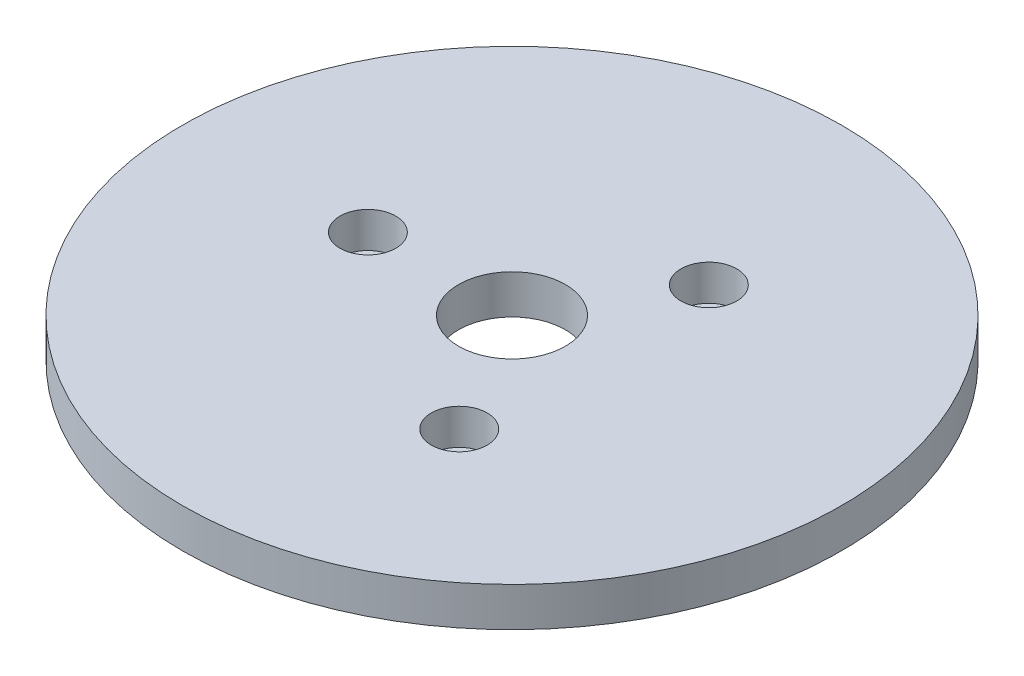
SolidWorks part; units mm, degrees
ref_plane "Front Plane" through (0, 0, 0) normal (0, 0, 1) x (1, 0, 0)
ref_plane "Top Plane" through (0, 0, 0) normal (0, 1, 0) x (1, 0, 0)
ref_plane "Right Plane" through (0, 0, 0) normal (1, 0, 0) x (0, 0, -1)
sketch "Sketch1" plane through (0, 0, 0) normal (0, 1, 0) x (1, 0, 0)
  circle A0 centre (0, 0) radius 92.5
  dimension "FLANGE_OD" = 185
extrude "Boss-Extrude1" add sketch "Sketch1" along normal blind 11
sketch "Sketch2" plane through (0, 0, 0) normal (0, 1, 0) x (1, 0, 0)
  circle A0 centre (0, 0) radius 15
  dimension "BORE_D" = 30
extrude "Cut-Extrude1" cut sketch "Sketch2" along normal through all
sketch "Sketch3" plane through (0, 11, 0) normal (0, 1, 0) x (1, 0, 0)
  circle A0 centre (0, 0) radius 40.4461 construction
  circle A1 centre (-40.4461, 0) radius 7.8376
  dimension "BOLT_D" = 15.6752
  dimension "BOLT_PCD" = 80.8922
extrude "Cut-Extrude2" cut sketch "Sketch3" against normal blind 10.0057
pattern_circular "CirPattern1" count 3 over 360 about axis through (0, 0, 0) along (0, 1, 0) of "Cut-Extrude2"
